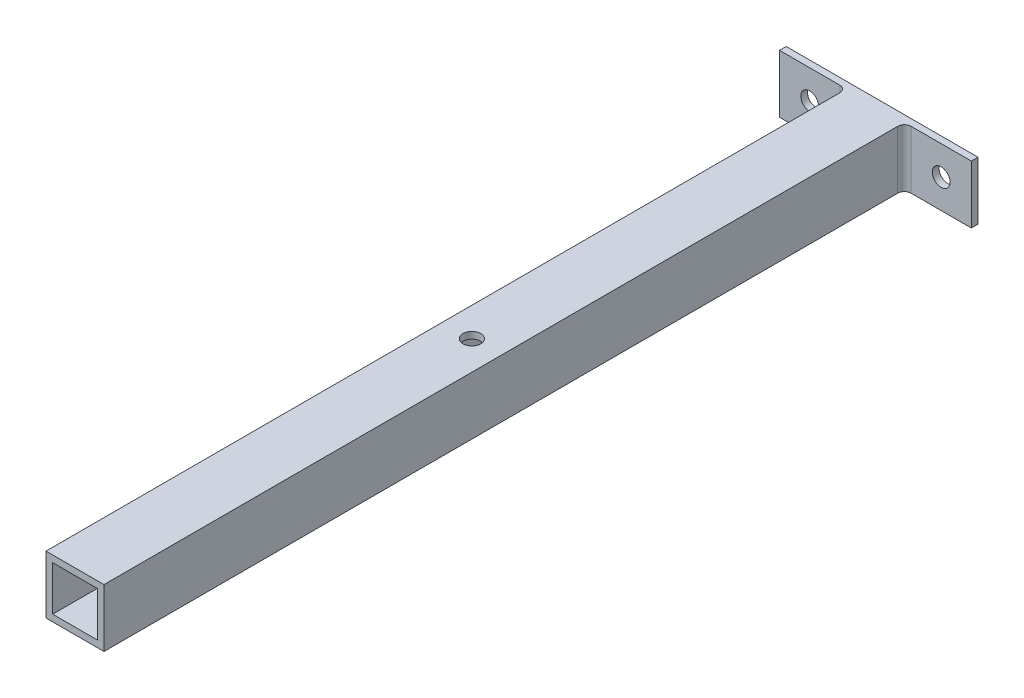
SolidWorks part; units mm, degrees
ref_plane "Front Plane" through (0, 0, 0) normal (0, 0, 1) x (1, 0, 0)
ref_plane "Top Plane" through (0, 0, 0) normal (0, 1, 0) x (1, 0, 0)
ref_plane "Right Plane" through (0, 0, 0) normal (1, 0, 0) x (0, 0, -1)
sketch "Sketch2" plane through (0, 0, 0) normal (0, 1, 0) x (1, 0, 0)
  line L0 (-13, 181) -> (-43, 181)
  line L1 (-13, 181) -> (13, 181)
  line L2 (-13, 178) -> (-13, -181)
  line L3 (-13, -181) -> (13, -181)
  line L4 (13, 178) -> (13, -181)
  line L5 (-13, 181) -> (13, -181) construction
  line L6 (-13, -181) -> (13, 181) construction
  line L7 (-43, 181) -> (-43, 178)
  line L8 (-43, 178) -> (-13, 178)
  line L9 (13, 181) -> (43, 181)
  line L10 (43, 181) -> (43, 178)
  line L11 (43, 178) -> (13, 178)
  point P0 (0, 0)
  dimension "D1" = 26
  dimension "D2" = 362
  dimension "D3" = 3
  dimension "D4" = 30
  dimension "D5" = 30
extrude "Boss-Extrude1" add sketch "Sketch2" along normal blind 26
shell "Shell1" thickness 3 removed face at (0, 13, -181) removed face at (0, 13, 181)
fillet "Fillet1" radius 3 4 edges at (-13, 13, -178) (13, 13, -178) (-10, 13, -181) (10, 13, -181)
sketch "Sketch3" plane through (0, 0, -178) normal (0, 0, 1) x (1, 0, 0)
  line L0 (29.5, 26) -> (29.5, 0) construction
  line L1 (16, 26) -> (43, 26) construction
  line L2 (16, 0) -> (43, 0) construction
  line L3 (0, 26) -> (0, 0) construction
  line L4 (-13, 26) -> (13, 26) construction
  circle A0 centre (29.5, 13) radius 4
  circle A1 centre (-29.5, 13) radius 4
  dimension "D1" = 8
extrude "Cut-Extrude1" cut sketch "Sketch3" against normal blind 3
sketch "Sketch4" plane through (0, 26, 0) normal (0, 1, 0) x (1, 0, 0)
  circle A0 centre (0, -3) radius 4
  dimension "D1" = 8
extrude "Cut-Extrude2" cut sketch "Sketch4" against normal blind 37
